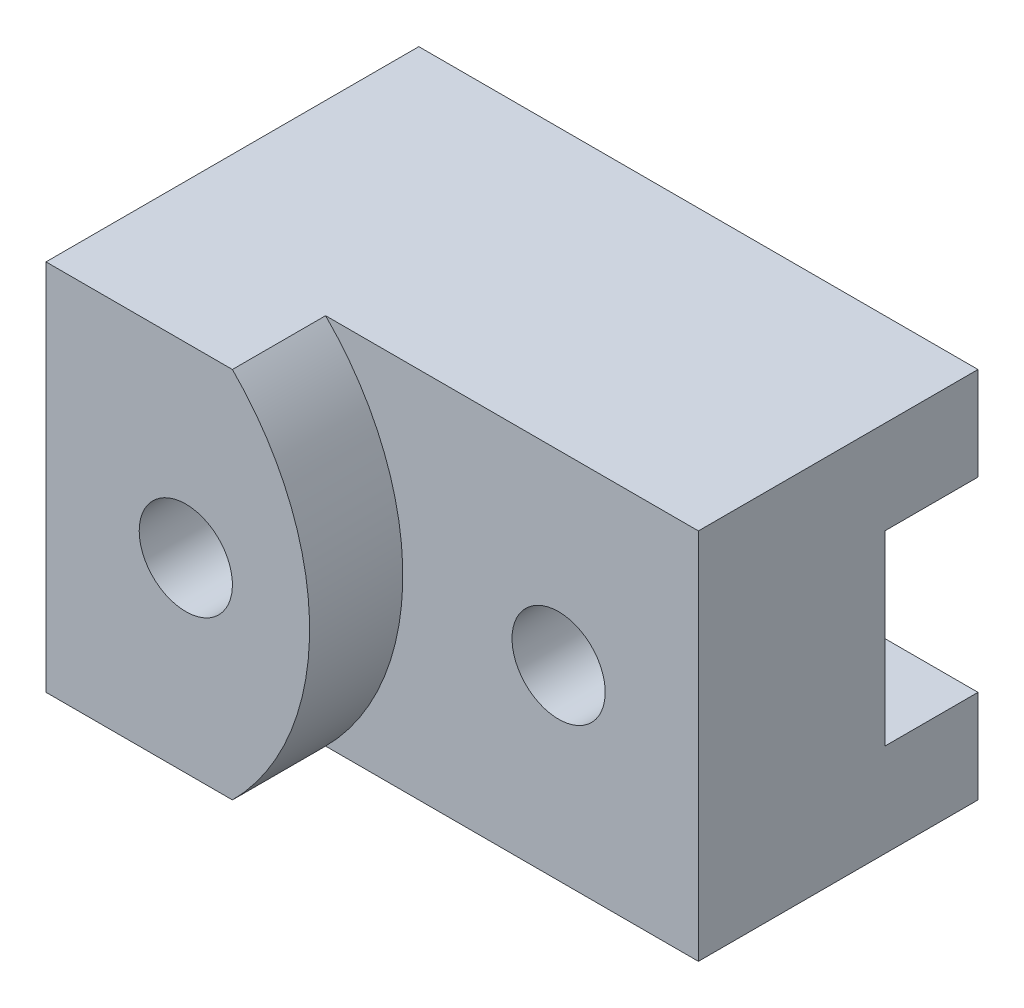
SolidWorks part; units mm, degrees
ref_plane "Front Plane" through (0, 0, 0) normal (0, 0, 1) x (1, 0, 0)
ref_plane "Top Plane" through (0, 0, 0) normal (0, 1, 0) x (1, 0, 0)
ref_plane "Right Plane" through (0, 0, 0) normal (1, 0, 0) x (0, 0, -1)
sketch "Sketch1" plane through (0, 0, 0) normal (1, 0, 0) x (0, 0, -1)
  line L1 (0, 0) -> (76.2, 0)
  line L2 (0, 0) -> (0, 101.6)
  line L3 (0, 101.6) -> (76.2, 101.6)
  line L4 (76.2, 0) -> (76.2, 101.6)
  line L5 (0, 0) -> (76.2, 101.6) construction
  line L6 (0, 101.6) -> (76.2, 0) construction
  line L7 (76.2, 25.4) -> (50.8, 25.4)
  line L8 (76.2, 25.4) -> (76.2, 76.2)
  line L9 (76.2, 76.2) -> (50.8, 76.2)
  line L10 (50.8, 25.4) -> (50.8, 76.2)
  line L11 (76.2, 25.4) -> (50.8, 76.2) construction
  line L12 (76.2, 76.2) -> (50.8, 25.4) construction
  point P4 (38.1, 50.8)
  point P10 (63.5, 50.8)
  point P11 (0, 0)
  point P12 (0, 0)
  point P13 (0, 0)
extrude "Boss-Extrude1" add sketch "Sketch1" against normal blind 152.4 contours L7 L10 L9 L4 L3 L2 L1 region at (0, 50.8, -33.02)
sketch "Sketch3" plane through (0, 0, -50.8) normal (0, 0, -1) x (-1, 0, 0)
  point P0 (38.1, 50.8)
  point P3 (0, 0)
hole_wizard "CBORE for 1/4 Binding Head Machine Screw1" positions "Sketch3" profile "Sketch4" counterbore size "1/4" standard "ANSI Inch" end condition through all
sketch "Sketch4" plane through (-38.1, 50.8, -50.8) normal (1, 0, 0) x (0, 1, 0)
  line L0 (0, 0) -> (0, 50.8)
  line L1 (0, 50.8) -> (12.7, 50.8)
  line L3 (12.7, 50.8) -> (12.7, 5.08)
  line L4 (12.7, 5.08) -> (19.05, 5.08)
  line L5 (19.05, 5.08) -> (19.05, 0)
  line L7 (19.05, 0) -> (0, 0)
  line L11 (0, -6.35) -> (0, 107.95) construction
  dimension "Thru Hole Dia." = 25.4
  dimension "Thru Hole Depth" = 50.8
  dimension "C'Bore Dia." = 38.1
  dimension "C'Bore Depth" = 5.08
sketch "Sketch5" plane through (0, 0, -50.8) normal (0, 0, -1) x (-1, 0, 0)
  circle A0 centre (114.3, 50.8) radius 12.7
  point P2 (0, 0)
  point P3 (125.4874, 50.8)
  point P4 (0, 0)
  point P5 (0, 0)
  dimension "D1" = 25.4
sketch "Sketch6" plane through (0, 0, 0) normal (0, 0, 1) x (1, 0, 0)
  line L0 (-152.4, 0) -> (0, 0) construction
  line L1 (-152.4, 101.6) -> (-101.6, 101.6)
  line L2 (-152.4, 101.6) -> (-152.4, 0)
  line L3 (-152.4, 0) -> (-101.6, 0)
  line L5 (-152.4, 101.6) -> (-101.6, 0) construction
  line L6 (-152.4, 0) -> (-101.6, 101.6) construction
  arc A0 (-101.6, 101.6) -> (-101.6, 0) centre (-152.4, 50.8) cw
  point P4 (-127, 50.8)
extrude "Boss-Extrude2" add sketch "Sketch6" along normal blind 25.4 contours A0 L3 L2 L1
extrude "Cut-Extrude2" cut sketch "Sketch5" against normal up to surface (76.2 mm away) up to face at (-121.7395, 50.8, 25.4)
